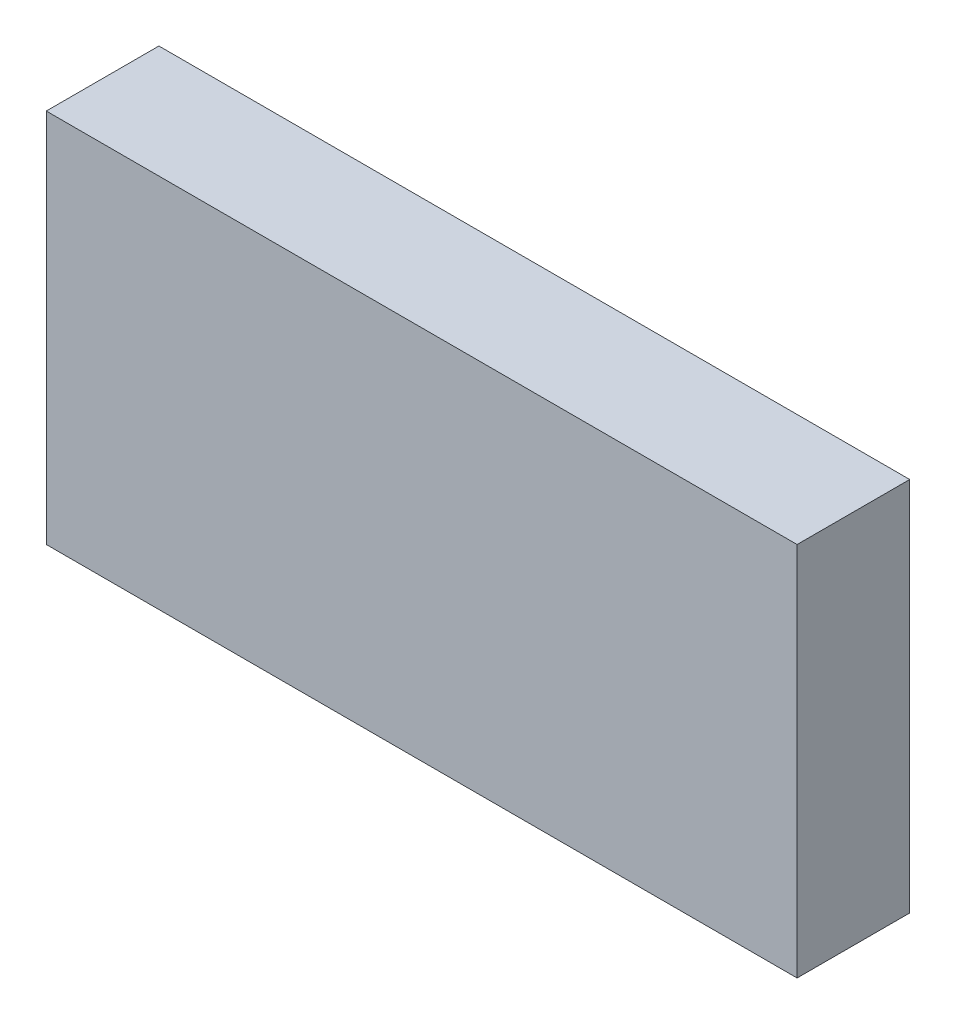
SolidWorks part; units mm, degrees
ref_plane "Front Plane" through (0, 0, 0) normal (0, 0, 1) x (1, 0, 0)
ref_plane "Top Plane" through (0, 0, 0) normal (0, 1, 0) x (1, 0, 0)
ref_plane "Right Plane" through (0, 0, 0) normal (1, 0, 0) x (0, 0, -1)
sketch "Sketch1" plane through (0, 0, 0) normal (0, 0, 1) x (1, 0, 0)
  line L1 (-1, -0.5) -> (1, -0.5)
  line L2 (-1, -0.5) -> (-1, 0.5)
  line L3 (-1, 0.5) -> (1, 0.5)
  line L4 (1, -0.5) -> (1, 0.5)
  line L5 (-1, -0.5) -> (1, 0.5) construction
  line L6 (-1, 0.5) -> (1, -0.5) construction
  point P0 (0, 0)
  dimension "D1" = 2
  dimension "D2" = 1
extrude "Boss-Extrude1" add sketch "Sketch1" along normal blind 0.3
